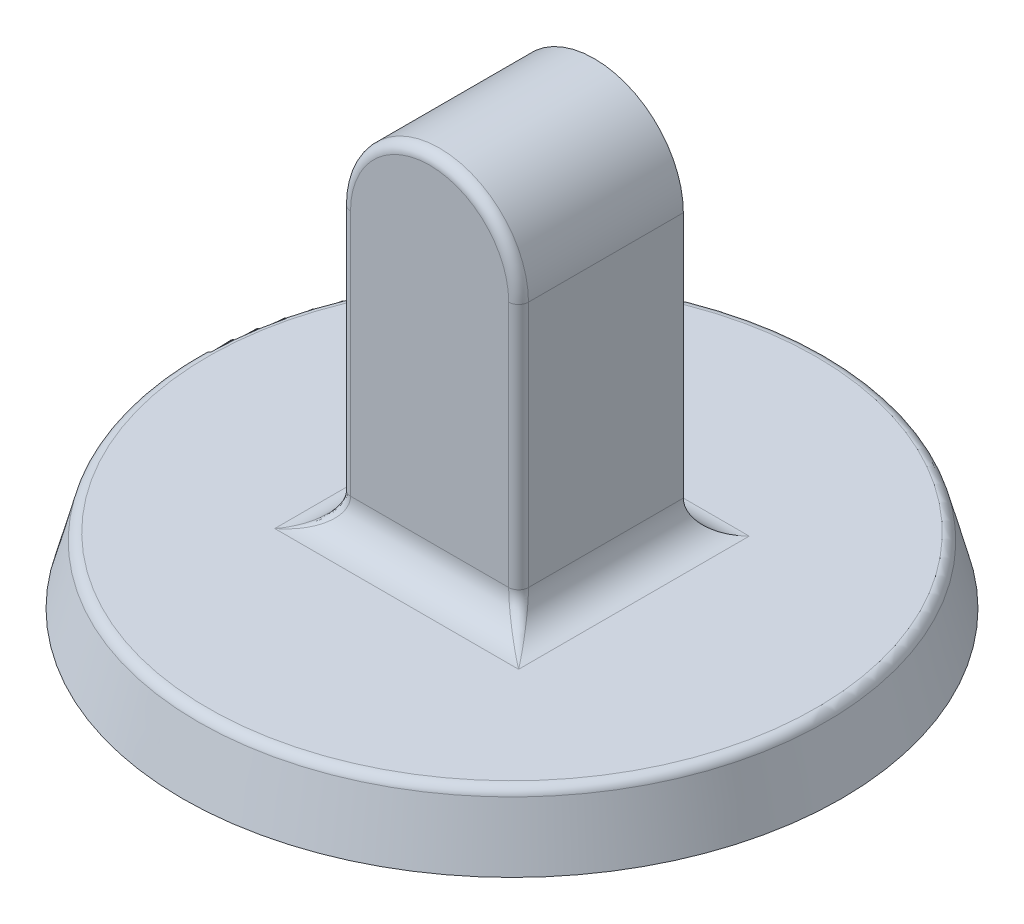
SolidWorks part; units mm, degrees
ref_plane "前基準面" through (0, 0, 0) normal (0, 0, 1) x (1, 0, 0)
ref_plane "上基準面" through (0, 0, 0) normal (0, 1, 0) x (1, 0, 0)
ref_plane "右基準面" through (0, 0, 0) normal (1, 0, 0) x (0, 0, -1)
sketch "草圖2" plane through (0, 0, 0) normal (0, 0, 1) x (1, 0, 0)
  line L0 (-3, -397.3542) -> (-3, -402.6458) construction
  line L1 (-3, -397.3542) -> (-3, -402.6458)
  line L2 (-27, -400) -> (-27, -485)
  line L3 (-27, -485) -> (27, -485)
  line L4 (27, -485) -> (27, -400)
  line L5 (21, -400) -> (-21, -400) construction
  circle A0 centre (0, -400) radius 27
  circle A1 centre (0, -400) radius 37 construction
  circle A2 centre (0, -400) radius 4
  arc A3 (0, -404) -> (0, -396) centre (0, -400) ccw construction
  dimension "D1" = 10
  dimension "D2" = 85
sketch "草圖4" plane through (0, 0, 0) normal (0, 0, 1) x (1, 0, 0)
  line L0 (-27, -485) -> (27, -485) construction
  line L1 (-27, -400) -> (-27, -485) construction
  line L2 (27, -485) -> (27, -400) construction
  line L3 (-27, -485) -> (27, -485)
  line L4 (-27, -400) -> (-27, -485)
  line L5 (27, -485) -> (27, -400)
  circle A0 centre (0, -400) radius 27 construction
  arc A1 (27, -400) -> (-27, -400) centre (0, -400) ccw
extrude "填料-伸長1" add sketch "草圖4" along normal blind 50
sketch "草圖5" plane through (0, -485, 0) normal (0, -1, 0) x (1, 0, 0)
  line L0 (27, 25) -> (-27, 25) construction
  line L1 (27, 50) -> (27, 0) construction
  line L2 (-27, 50) -> (-27, 0) construction
  line L3 (0, 0) -> (0, 50) construction
  line L4 (-27, 50) -> (27, 50) construction
  circle A0 centre (0, 25) radius 100
  dimension "D1" = 200
extrude "填料-伸長2" add sketch "草圖5" along normal blind 20
sketch "草圖6" plane through (0, -505, 0) normal (0, -1, 0) x (1, 0, 0)
  circle A0 centre (0, 25) radius 90
  circle A1 centre (0, 25) radius 100 construction
  dimension "D1" = 10
extrude "除料-伸長1" cut sketch "草圖6" against normal offset from surface (10 mm away) 10 up to face at (0, -485, -75)
draft "拔模1" type of draft neutral plane draft angle 15 faces to draft 1 face at (0, -505, -75) neutral plane through (0, -505, 25) neutral plane normal (0, -1, 0) reverse direction yes parameters "D1"=15
fillet "圓角1" radius 10 4 edges at (0, -485, 50) (-27, -485, 25) (27, -485, 25) (0, -485, 0)
fillet "圓角2" radius 3 1 edges at (0, -485, -69.641)
fillet "圓角3" radius 3 5 edges at (29.9289, -482.0711, 52.9289) (-29.9289, -482.0711, 52.9289) (-27, -437.5, 50) (0, -373, 50) (27, -437.5, 50)
